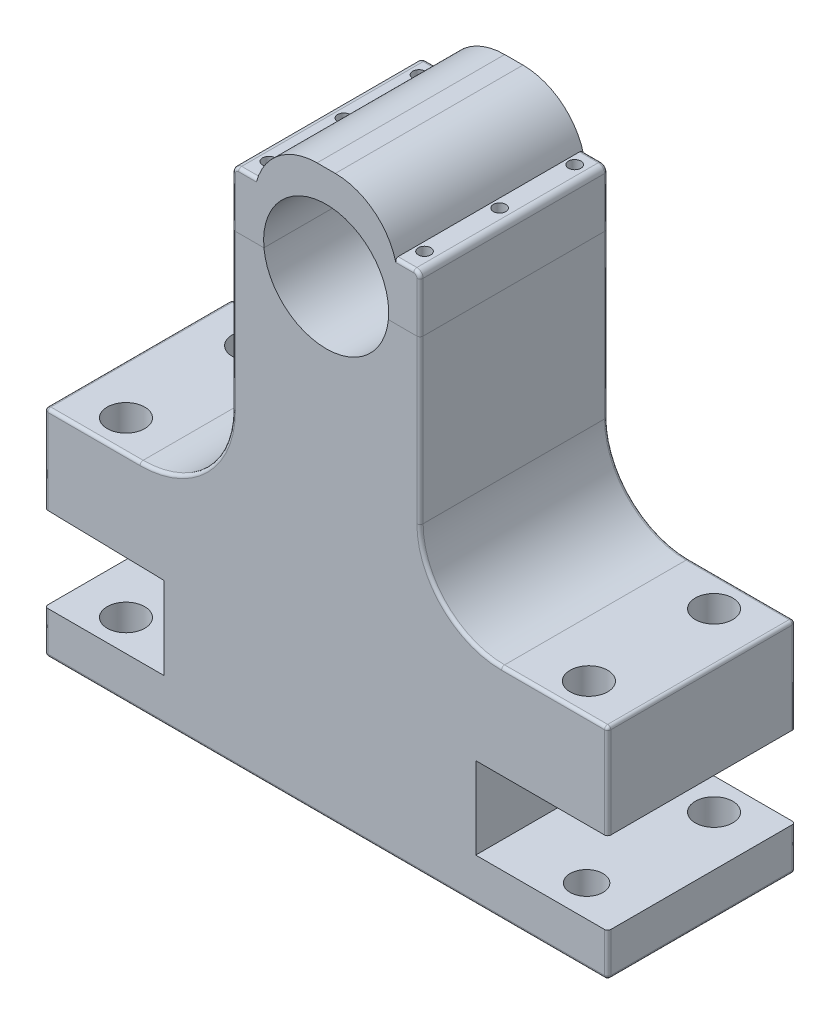
SolidWorks part; units mm, degrees
ref_plane "Plan de face" through (0, 0, 0) normal (0, 0, 1) x (1, 0, 0)
ref_plane "Plan de dessus" through (0, 0, 0) normal (0, 1, 0) x (1, 0, 0)
ref_plane "Plan de droite" through (0, 0, 0) normal (1, 0, 0) x (0, 0, -1)
sketch "Esquisse1" plane through (0, 0, 0) normal (0, 0, 1) x (1, 0, 0)
  line L0 (0, 0) -> (900, 0)
  line L1 (900, 0) -> (900, 150)
  line L3 (0, 144.3329) -> (0, 0)
  line L4 (300, 374.9177) -> (300, 630)
  line L5 (340, 700) -> (560, 700)
  line L6 (600, 630) -> (600, 375)
  line L7 (0, 144.3329) -> (152.4789, 144.3329)
  line L8 (300, 291.854) -> (300, 374.9177)
  line L9 (900, 150) -> (730.278, 150)
  line L10 (600, 375) -> (600, 280.278)
  line L11 (560, 700) -> (560, 630)
  line L12 (560, 630) -> (600, 630)
  line L16 (300, 630) -> (340, 630)
  line L17 (340, 700) -> (340, 630)
  circle A2 centre (450, 550) radius 100
  arc A3 (152.4789, 144.3329) -> (300, 291.854) centre (152.4789, 291.854) ccw
  arc A4 (730.278, 150) -> (600, 280.278) centre (730.278, 280.278) cw
  point P6 (320, 630)
  dimension "D1" = 200
  dimension "D2" = 550
  dimension "D3" = 40
  dimension "D4" = 700
  dimension "D5" = 40
  dimension "D6" = 300
  dimension "D7" = 900
  dimension "D8" = 450
  dimension "D9" = 70
  dimension "D10" = 70
extrude "Boss.-Extru.1" add sketch "Esquisse1" against normal blind 300
sketch "Esquisse2" plane through (0, 144.3329, 0) normal (0, 1, 0) x (1, 0, 0)
  line L0 (152.4789, 300) -> (0, 300) construction
  line L1 (152.4789, 0) -> (0, 0) construction
  line L2 (0, 300) -> (0, 0) construction
  circle A0 centre (80, 250) radius 30
  circle A1 centre (80, 50) radius 30
  dimension "D1" = 60
  dimension "D2" = 60
  dimension "D3" = 50
  dimension "D4" = 50
  dimension "D5" = 80
  dimension "D6" = 80
extrude "Enlèv. mat.-Extru.1" cut sketch "Esquisse2" against normal blind 500
fillet "Congé3" radius 100 2 edges at (340, 700, -150) (560, 700, -150)
fillet "Congé4" radius 10 2 edges at (300, 630, -150) (600, 630, -150)
sketch "Esquisse3" plane through (0, 150, 0) normal (0, 1, 0) x (1, 0, 0)
  line L0 (900, 300) -> (730.278, 300) construction
  line L1 (900, 0) -> (730.278, 0) construction
  line L2 (900, 300) -> (900, 0) construction
  circle A0 centre (820, 250) radius 30
  circle A1 centre (820, 50) radius 30
  dimension "D1" = 60
  dimension "D2" = 60
  dimension "D3" = 50
  dimension "D4" = 50
  dimension "D5" = 80
  dimension "D6" = 80
extrude "Enlèv. mat.-Extru.2" cut sketch "Esquisse3" against normal blind 500
sketch "Esquisse4" plane through (0, 630, 0) normal (0, 1, 0) x (1, 0, 0)
  circle A0 centre (573.7843, 273.4522) radius 10
  circle A1 centre (324.8854, 273.4522) radius 10
  dimension "D1" = 20
  dimension "D2" = 20
extrude "Enlèv. mat.-Extru.3" cut sketch "Esquisse4" against normal blind 200
pattern_linear "Répétition linéaire1" count 3 spacing 120 along (0, 0, 1) of "Enlèv. mat.-Extru.3"
sketch "Esquisse6" plane through (0, 0, 0) normal (0, 0, 1) x (1, 0, 0)
  line L0 (0, 0) -> (0, -200)
  line L1 (0, -200) -> (900, -200)
  line L2 (900, -200) -> (900, 0)
  line L3 (0, 0) -> (900, 0) construction
  line L4 (0, 0) -> (900, 0)
  dimension "D1" = 200
extrude "Boss.-Extru.2" add sketch "Esquisse6" against normal blind 300
sketch "Esquisse7" plane through (0, 0, 0) normal (0, 1, 0) x (1, 0, 0)
  circle A0 centre (80.6625, 253.0556) radius 33.1266
  circle A1 centre (80, 50) radius 30
  circle A2 centre (816.2966, 50) radius 26.2966
  circle A3 centre (820, 250) radius 30
extrude "Enlèv. mat.-Extru.4" cut sketch "Esquisse7" against normal blind 300
fillet "Congé6" radius 5 30 edges at (815.139, 150, 0) (575, 630, 0) (597.0711, 627.0711, 0) (600, 450.139, 0) (815.139, 150, -300) (575, 630, -300) (597.0711, 627.0711, -300) (600, 450.139, -300) (325, 630, -300) (302.9289, 627.0711, -300) (300, 455.927, -300) (256.7921, 187.5409, -300) (325, 630, 0) (302.9289, 627.0711, 0) (76.2395, 144.3329, 0) (256.7921, 187.5409, 0) (900, -200, -150) (450, -200, -300) (0, -200, -150) (450, -200, 0) (638.1576, 188.1576, 0) (900, 150, -150) (900, -25, 0) (900, -25, -300) (638.1576, 188.1576, -300) (76.2395, 144.3329, -300) (0, -27.8335, -300) (0, 144.3329, -150) (0, -27.8335, 0) (300, 455.927, 0)
ref_plane "Plan1" through (0, 540, 0) normal (0, -1, 0) x (-1, 0, 0)
split "Fractionner1" trim tools "Plan1" bodies to split 107 resulting bodies 108 109
sketch "Esquisse8" plane through (0, 0, -300) normal (0, 0, -1) x (-1, 0, 0)
  line L0 (-5, 3.6453) -> (-191.0727, -0.3189)
  line L1 (-5, -195) -> (-5, 139.3329) construction
  line L2 (-191.0727, -0.3189) -> (-191.0727, -131.9886)
  line L3 (-191.0727, -131.9886) -> (-5, -131.9886)
  line L4 (-5, -131.9886) -> (-5, 3.6453)
  line L5 (-5, 3.6453) -> (0, 3.3662)
  line L6 (0, 3.3662) -> (0, -131.9886)
  line L7 (0, -131.9886) -> (-5, -131.9886)
  line M11 (-5, -195) -> (-5, 139.3329)
extrude "Enlèv. mat.-Extru.6" cut sketch "Esquisse8" against normal blind 300 contours L2 L3 L0 M11 | L7 L6 L5 M11 region at (97.5765, -65.1578, -300) region at (2.5009, -64.2414, -300)
sketch "Esquisse9" plane through (0, 0, -300) normal (0, 0, -1) x (-1, 0, 0)
  line L0 (-689.1123, -0.6587) -> (-895, -0.6587)
  line L1 (-895, 145) -> (-895, -195) construction
  line L2 (-689.1123, -0.6587) -> (-689.1123, -131.4044)
  line L3 (-689.1123, -131.4044) -> (-895, -131.4044)
  line L4 (-895, -131.4044) -> (-895, -0.6587)
  line L5 (-895, -0.6587) -> (-900.4685, -0.6587)
  line L6 (-900.4685, -0.6587) -> (-900.4685, -131.4044)
  line L7 (-900.4685, -131.4044) -> (-895, -131.4044)
  line M12 (-895, 145) -> (-895, -195)
extrude "Enlèv. mat.-Extru.7" cut sketch "Esquisse9" against normal blind 300 contours L6 L7 L5 M12 | L3 L2 L0 M12 region at (792.0562, -66.0316, -300) region at (897.7342, -66.0316, -300)
